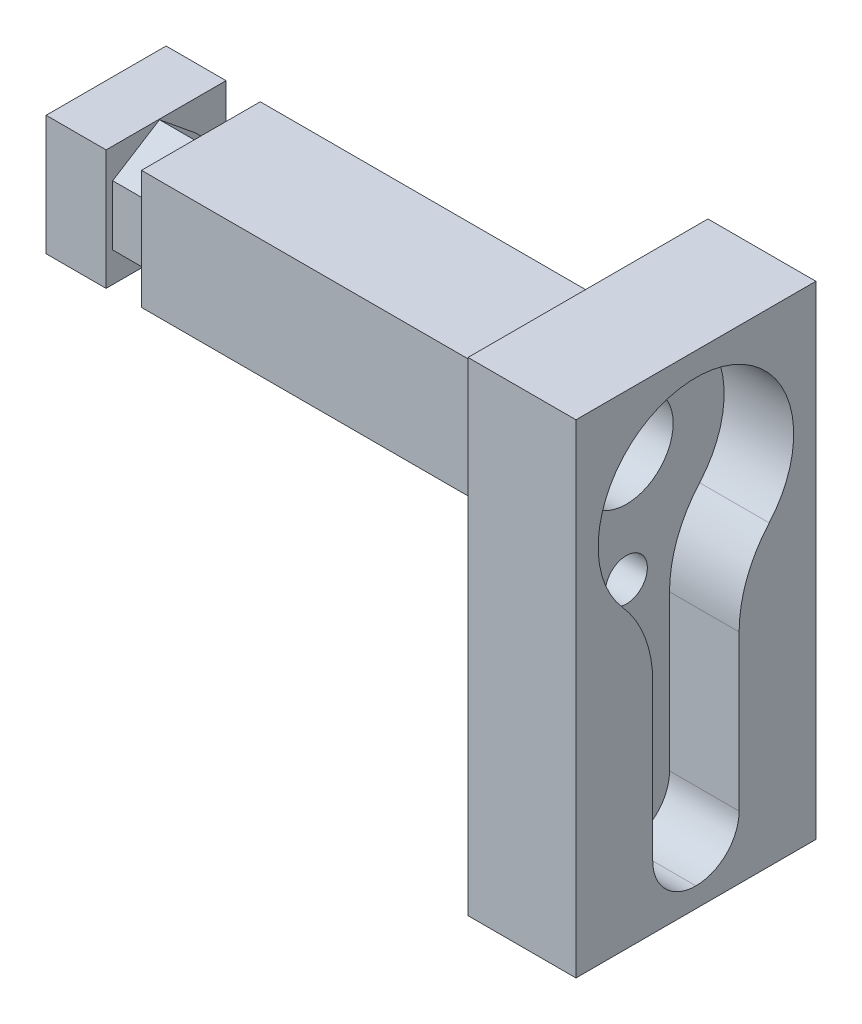
SolidWorks part; units mm, degrees
ref_plane "Front Plane" through (0, 0, 0) normal (0, 0, 1) x (1, 0, 0)
ref_plane "Top Plane" through (0, 0, 0) normal (0, 1, 0) x (1, 0, 0)
ref_plane "Right Plane" through (0, 0, 0) normal (1, 0, 0) x (0, 0, -1)
sketch "Sketch1" plane through (0, 0, 0) normal (1, 0, 0) x (0, 0, -1)
  line L1 (-10, 10) -> (10, 10)
  line L2 (-10, 10) -> (-10, -10)
  line L3 (-10, -10) -> (10, -10)
  line L4 (10, 10) -> (10, -10)
  line L5 (-10, 10) -> (10, -10) construction
  line L6 (-10, -10) -> (10, 10) construction
  point P0 (0, 0)
  dimension "D1" = 20
  dimension "D2" = 20
extrude "Boss-Extrude1" add sketch "Sketch1" along normal blind 20
sketch "Sketch2" plane through (20, 0, 0) normal (1, 0, 0) x (0, 0, -1)
  line L1 (-22.5, 35) -> (22.5, 35)
  line L2 (-22.5, 35) -> (-22.5, -35)
  line L3 (-22.5, -35) -> (22.5, -35)
  line L4 (22.5, 35) -> (22.5, -35)
  line L5 (-22.5, 35) -> (22.5, -35) construction
  line L6 (-22.5, -35) -> (22.5, 35) construction
  point P0 (0, 0)
  dimension "D1" = 45
  dimension "D2" = 70
extrude "Boss-Extrude2" add sketch "Sketch2" along normal blind 12
sketch "Sketch4" plane through (32, 0, 0) normal (1, 0, 0) x (0, 0, -1)
  line L0 (0, 7.65) -> (0, 8.1702) construction
  line L1 (7.65, 7.65) -> (-7.65, 7.65) construction
  line L17 (3.6, -26.55) -> (-3.6, -26.55) construction
  line L18 (-7.65, 7.65) -> (7.65, 7.65) construction
  line L22 (-7.65, 7.65) -> (-7.65, -27.55) construction
  line L23 (-7.65, -27.55) -> (7.65, -27.55) construction
  line L24 (7.65, 7.65) -> (7.65, -27.55) construction
  line L25 (-7.65, 7.65) -> (7.65, -27.55) construction
  line L26 (-7.65, -27.55) -> (7.65, 7.65) construction
  line L27 (3.6, -26.55) -> (3.6, -28.55) construction
  line L28 (3.6, -28.55) -> (-3.6, -28.55) construction
  line L29 (-3.6, -26.55) -> (-3.6, -28.55) construction
  line L30 (3.6, -26.55) -> (-3.6, -28.55) construction
  line L31 (3.6, -28.55) -> (-3.6, -26.55) construction
  line L34 (3.6, -28.55) -> (-3.6, -28.55)
  line L35 (-3.6, -28.55) -> (-3.6, -7.3118)
  line L36 (3.6, -28.55) -> (3.6, -7.3118)
  arc A1 (3.6, -6.75) -> (-3.6, -6.75) centre (0, 0) ccw construction
  arc A2 (3.6, -7.3118) -> (-3.6, -7.3118) centre (0, 0) ccw
  point P1 (0, -27.55)
  point P7 (0, -13.75)
  point P10 (0, 7.65)
  point P14 (0, -9.95)
  dimension "D1" = 15.3
  dimension "D5" = 2
  dimension "D2" = 15.3
  dimension "D3" = 35.2
  dimension "D4" = 7.2
extrude "Cut-Extrude1" cut sketch "Sketch4" against normal blind 5.8
fillet "Fillet1" radius 3.6 2 edges at (29.1, -28.55, 3.6) (29.1, -28.55, -3.6)
fillet "Fillet2" radius 10 2 edges at (29.1, -7.3118, 3.6) (29.1, -7.3118, -3.6)
sketch "Sketch5" plane through (0, 0, 0) normal (-1, 0, 0) x (0, 0, 1)
  circle A0 centre (0, 0) radius 3.9
  dimension "D1" = 7.8
extrude "Cut-Extrude2" cut sketch "Sketch5" against normal through all
sketch "Sketch6" plane through (26.2, 0, 0) normal (1, 0, 0) x (0, 0, -1)
  line L0 (0, -19.35) -> (0, 0) construction
  line L1 (0, -25.65) -> (0, -23.15) construction
  line L2 (0, -23.15) -> (0, -21.85) construction
  line L3 (0, -21.85) -> (0, -19.35) construction
  line L5 (0, 0) -> (1.164, 0) construction
  line L6 (0, 0) -> (0, -9.35) construction
  line L7 (0, -9.35) -> (1.164, -9.35) construction
  line L8 (1.164, 0) -> (1.164, -9.35) construction
  line L9 (0, 0) -> (1.164, -9.35) construction
  line L10 (0, -9.35) -> (1.164, 0) construction
  circle A0 centre (0, -20.6) radius 1.75
  circle A1 centre (0, -9.35) radius 1.75
  point P11 (0.582, -4.675)
  dimension "D5" = 3.5
  dimension "D6" = 9.35
  dimension "D7" = 3.5
  dimension "D1" = 19.35
  dimension "D2" = 2.5
  dimension "D3" = 1.3
  dimension "D4" = 2.5
extrude "Cut-Extrude3" cut sketch "Sketch6" against normal up to next
sketch "Sketch7" plane through (0, -35, 0) normal (0, -1, 0) x (1, 0, 0)
  line L1 (32, 22.5) -> (20, 22.5)
  line L2 (32, 22.5) -> (32, -22.5)
  line L3 (32, -22.5) -> (20, -22.5)
  line L4 (20, 22.5) -> (20, -22.5)
  line L5 (32, 22.5) -> (20, -22.5) construction
  line L6 (32, -22.5) -> (20, 22.5) construction
  point P5 (26, 0)
extrude "Cut-Extrude4" cut sketch "Sketch7" against normal blind 4.8
sketch "Sketch9" plane through (0, 35, 0) normal (0, 1, 0) x (1, 0, 0)
  line L1 (32, 22.5) -> (20, 22.5)
  line L2 (32, 22.5) -> (32, -22.5)
  line L3 (32, -22.5) -> (20, -22.5)
  line L4 (20, 22.5) -> (20, -22.5)
  line L5 (32, 22.5) -> (20, -22.5) construction
  line L6 (32, -22.5) -> (20, 22.5) construction
  point P4 (26, 0)
extrude "Cut-Extrude5" cut sketch "Sketch9" against normal blind 23.8
sketch "Sketch10" plane through (20, 0, 0) normal (-1, 0, 0) x (0, 0, 1)
  line L0 (-22.5, 11.2) -> (22.5, 11.2) construction
  line L1 (-10, 11.2) -> (-22.5, 11.2)
  line L2 (-10, 11.2) -> (-10, -30.2)
  line L3 (-10, -30.2) -> (-22.5, -30.2)
  line L4 (-22.5, 11.2) -> (-22.5, -30.2)
  line L5 (-10, 11.2) -> (-22.5, -30.2) construction
  line L6 (-10, -30.2) -> (-22.5, 11.2) construction
  line L7 (22.5, -30.2) -> (-22.5, -30.2) construction
  line L9 (10, 11.2) -> (22.5, 11.2)
  line L10 (10, 11.2) -> (10, -30.2)
  line L11 (10, -30.2) -> (22.5, -30.2)
  line L12 (22.5, 11.2) -> (22.5, -30.2)
  line L13 (10, 11.2) -> (22.5, -30.2) construction
  line L14 (10, -30.2) -> (22.5, 11.2) construction
  point P4 (-16.25, -9.5)
  point P13 (16.25, -9.5)
extrude "Cut-Extrude6" cut sketch "Sketch10" against normal blind 23.8
sketch "Sketch11" plane through (20, 0, 0) normal (-1, 0, 0) x (0, 0, 1)
  line L5 (-10, 11.2) -> (10, 11.2)
  line L6 (-10, 11.2) -> (-10, 10)
  line L7 (-10, 10) -> (10, 10)
  line L8 (10, 11.2) -> (10, 10)
  line L9 (-10, 11.2) -> (10, 10) construction
  line L10 (-10, 10) -> (10, 11.2) construction
  point P4 (0, 10.6)
extrude "Cut-Extrude7" cut sketch "Sketch11" against normal blind 23.8
sketch "Sketch12" plane through (0, 0, 0) normal (-1, 0, 0) x (0, 0, 1)
  line L1 (10, 10) -> (-10, 10)
  line L2 (10, 10) -> (10, -10)
  line L3 (10, -10) -> (-10, -10)
  line L4 (-10, 10) -> (-10, -10)
  line L5 (10, 10) -> (-10, -10) construction
  line L6 (10, -10) -> (-10, 10) construction
  circle A0 centre (0, 0) radius 3.9
  point P4 (0, 0)
extrude "Boss-Extrude3" add sketch "Sketch12" along normal blind 20
sketch "Sketch13" plane through (-20, 0, 0) normal (-1, 0, 0) x (0, 0, 1)
  line L8 (10.1, -10.1) -> (10.1, 10.1)
  line L9 (10.1, 10.1) -> (-10.1, 10.1)
  line L10 (-10.1, 10.1) -> (-10.1, -10.1)
  line L11 (-10.1, -10.1) -> (10.1, -10.1)
  line L12 (10.1, -10.1) -> (10.1, 10.1)
  line L13 (10.1, 10.1) -> (-10.1, 10.1)
  line L14 (-10.1, 10.1) -> (-10.1, -10.1)
  line L15 (-10.1, -10.1) -> (10.1, -10.1)
  circle A0 centre (0, 0) radius 3.9
  dimension "D1" = 0.1
extrude "Boss-Extrude4" add sketch "Sketch13" against normal up to surface (40 mm away) up to face at (20, -20.6, -1.75)
sketch "Sketch14" plane through (0, 10, 0) normal (0, 1, 0) x (1, 0, 0)
  line L1 (32, 10) -> (20, 10)
  line L2 (32, 10) -> (32, -10)
  line L3 (32, -10) -> (20, -10)
  line L4 (20, 10) -> (20, -10)
  line L5 (32, 10) -> (20, -10) construction
  line L6 (32, -10) -> (20, 10) construction
  point P4 (26, 0)
extrude "Boss-Extrude5" add sketch "Sketch14" along normal blind 0.1
sketch "Sketch17" plane through (-20, 0, 0) normal (-1, 0, 0) x (0, 0, 1)
  circle A0 centre (0, 0) radius 4.8309
extrude "Boss-Extrude8" add sketch "Sketch17" against normal blind 39
sketch "Sketch18" plane through (-20, 0, 0) normal (-1, 0, 0) x (0, 0, 1)
  line L5 (10.1, 10.1) -> (-15.5388, 10.1)
  line L6 (10.1, 10.1) -> (10.1, -36.522)
  line L7 (10.1, -36.522) -> (-15.5388, -36.522)
  line L8 (-15.5388, 10.1) -> (-15.5388, -36.522)
  line L9 (10.1, 10.1) -> (-15.5388, -36.522) construction
  line L10 (10.1, -36.522) -> (-15.5388, 10.1) construction
  point P4 (-2.7194, -13.211)
extrude "Cut-Extrude8" cut sketch "Sketch18" against normal blind 43
sketch "Sketch19" plane through (23, 0, 0) normal (-1, 0, 0) x (0, 0, 1)
  line L1 (4.95, 4.95) -> (-4.95, 4.95)
  line L2 (4.95, 4.95) -> (4.95, -4.95)
  line L3 (4.95, -4.95) -> (-4.95, -4.95)
  line L4 (-4.95, 4.95) -> (-4.95, -4.95)
  line L5 (4.95, 4.95) -> (-4.95, -4.95) construction
  line L6 (4.95, -4.95) -> (-4.95, 4.95) construction
  point P0 (0, 0)
  dimension "D1" = 9.9
  dimension "D2" = 9.9
extrude "Boss-Extrude9" add sketch "Sketch19" along normal blind 32.27
sketch "Sketch20" plane through (-9.27, 0, 0) normal (-1, 0, 0) x (0, 0, 1)
  line L0 (-4.95, 0) -> (-4.95, 2.5) construction
  line L1 (-4.95, 4.95) -> (-4.95, -4.95) construction
  line L2 (-4.95, 0) -> (-4.95, -2.5) construction
  line L3 (-4.95, 2.5) -> (4.95, 2.5) construction
  line L4 (4.95, -4.95) -> (4.95, 4.95) construction
  line L5 (-4.95, -2.5) -> (4.95, -2.5) construction
  line L6 (-4.95, 4.95) -> (0.55, 4.95) construction
  line L7 (4.95, 4.95) -> (-4.95, 4.95) construction
  line L8 (-4.95, -4.95) -> (0.55, -4.95) construction
  line L9 (-4.95, -4.95) -> (4.95, -4.95) construction
  line L10 (0.55, 4.95) -> (-2.45, 2.5)
  line L11 (-4.95, 2.5) -> (-2.45, 2.5) construction
  line L12 (0.55, 4.95) -> (4.45, 2.5)
  line L13 (4.95, 2.5) -> (4.45, 2.5) construction
  line L14 (4.95, 2.5) -> (4.95, -2.5) construction
  line L15 (4.95, -2.5) -> (4.45, -2.5) construction
  line L16 (4.45, 2.5) -> (4.45, -2.5) construction
  line L17 (4.95, 2.5) -> (4.45, -2.5) construction
  line L18 (4.95, -2.5) -> (4.45, 2.5) construction
  line L19 (4.45, 2.5) -> (4.45, -2.5)
  line L20 (4.45, -2.5) -> (0.55, -4.95)
  line L21 (-4.95, 2.5) -> (-4.95, -2.5) construction
  line L22 (-4.95, -2.5) -> (-2.45, -2.5) construction
  line L23 (-2.45, 2.5) -> (-2.45, -2.5) construction
  line L24 (-4.95, 2.5) -> (-2.45, -2.5) construction
  line L25 (-4.95, -2.5) -> (-2.45, 2.5) construction
  line L26 (-2.45, 2.5) -> (-2.45, -2.5)
  line L27 (-2.45, -2.5) -> (0.55, -4.95)
  point P21 (4.7, 0)
  point P24 (-3.7, 0)
  dimension "D1" = 2.5
  dimension "D2" = 2.5
  dimension "D3" = 5.5
  dimension "D4" = 5.5
  dimension "D5" = 0.5
  dimension "D6" = 2.5
extrude "Boss-Extrude10" add sketch "Sketch20" along normal blind 2.9
sketch "Sketch21" plane through (-12.17, 0, 0) normal (-1, 0, 0) x (0, 0, 1)
  line L1 (5, 5) -> (-5, 5)
  line L2 (5, 5) -> (5, -5)
  line L3 (5, -5) -> (-5, -5)
  line L4 (-5, 5) -> (-5, -5)
  line L5 (5, 5) -> (-5, -5) construction
  line L6 (5, -5) -> (-5, 5) construction
  point P0 (0, 0)
  dimension "D1" = 10
  dimension "D2" = 10
extrude "Boss-Extrude11" add sketch "Sketch21" along normal blind 5
fillet "Fillet4" radius 4 3 edges at (23, 0, 4.95) (23, 4.95, 0) (23, 0, -4.95)
fillet "Fillet5" radius 1 1 edges at (23, -4.95, 0)
